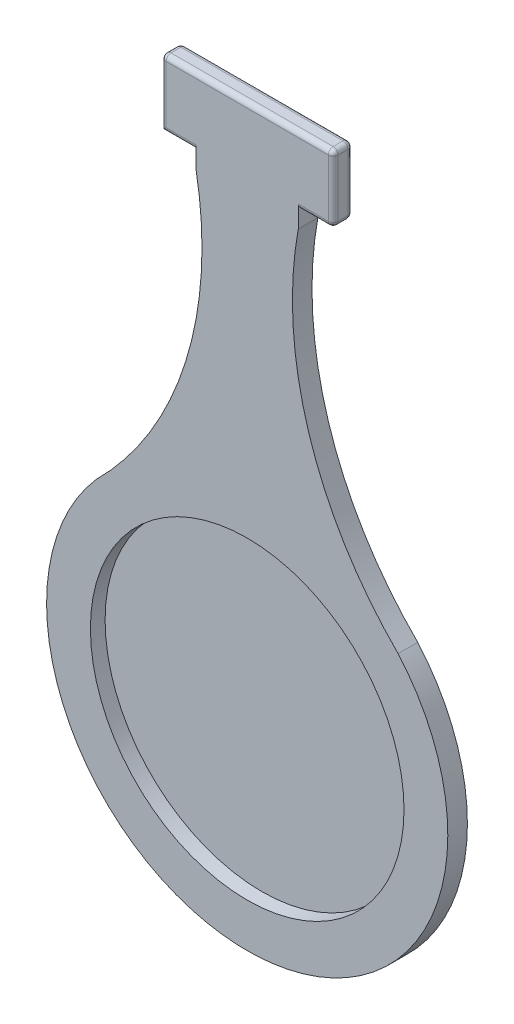
SolidWorks part; units mm, degrees
ref_plane "前视基准面" through (0, 0, 0) normal (0, 0, 1) x (1, 0, 0)
ref_plane "上视基准面" through (0, 0, 0) normal (0, 1, 0) x (1, 0, 0)
ref_plane "右视基准面" through (0, 0, 0) normal (1, 0, 0) x (0, 0, -1)
sketch "草图4" plane through (0, 0, 0) normal (0, 0, 1) x (1, 0, 0)
  line L0 (10.4264, 95.2581) -> (17.5474, 95.2581)
  line L2 (-10.4264, 91.8315) -> (-10.4264, 95.2581)
  line L4 (10.4264, 91.8315) -> (10.4264, 95.2581)
  line L5 (-17.5474, 108.961) -> (17.5474, 108.961)
  line L6 (-17.5474, 108.961) -> (-17.5474, 95.2581)
  line L7 (-17.5474, 95.2581) -> (-10.4264, 95.2581)
  line L8 (17.5474, 108.961) -> (17.5474, 95.2581)
  arc A1 (-30.794, 26.9767) -> (-10.4264, 91.8315) centre (-81.9478, 78.6671) ccw
  arc A2 (-30.794, 26.9767) -> (30.794, 26.9767) centre (0, 0) ccw
  arc A3 (30.794, 26.9767) -> (10.4264, 91.8315) centre (81.9478, 78.6671) cw
  point P14 (0, 102.1096)
extrude "凸台-拉伸2" add sketch "草图4" along normal blind 4
sketch "草图5" plane through (0, 0, 4) normal (0, 0, 1) x (1, 0, 0)
  circle A0 centre (0, 0) radius 32
extrude "切除-拉伸2" cut sketch "草图5" against normal blind 3
fillet "圆角7" radius 1 11 edges at (-13.9869, 95.2581, 4) (-13.9869, 95.2581, 0) (13.9869, 95.2581, 0) (13.9869, 95.2581, 4) (-17.5474, 102.1096, 0) (-17.5474, 102.1096, 4) (17.5474, 95.2581, 2) (0, 108.961, 0) (0, 108.961, 4) (17.5474, 102.1096, 4) (17.5474, 102.1096, 0)
fillet "圆角8" radius 1 6 edges at (-17.2545, 108.6681, 3.7071) (-17.2545, 108.6681, 0.2929) (17.2545, 108.6681, 3.7071) (17.2545, 108.6681, 0.2929) (-17.5474, 108.961, 2) (17.5474, 108.961, 2)
